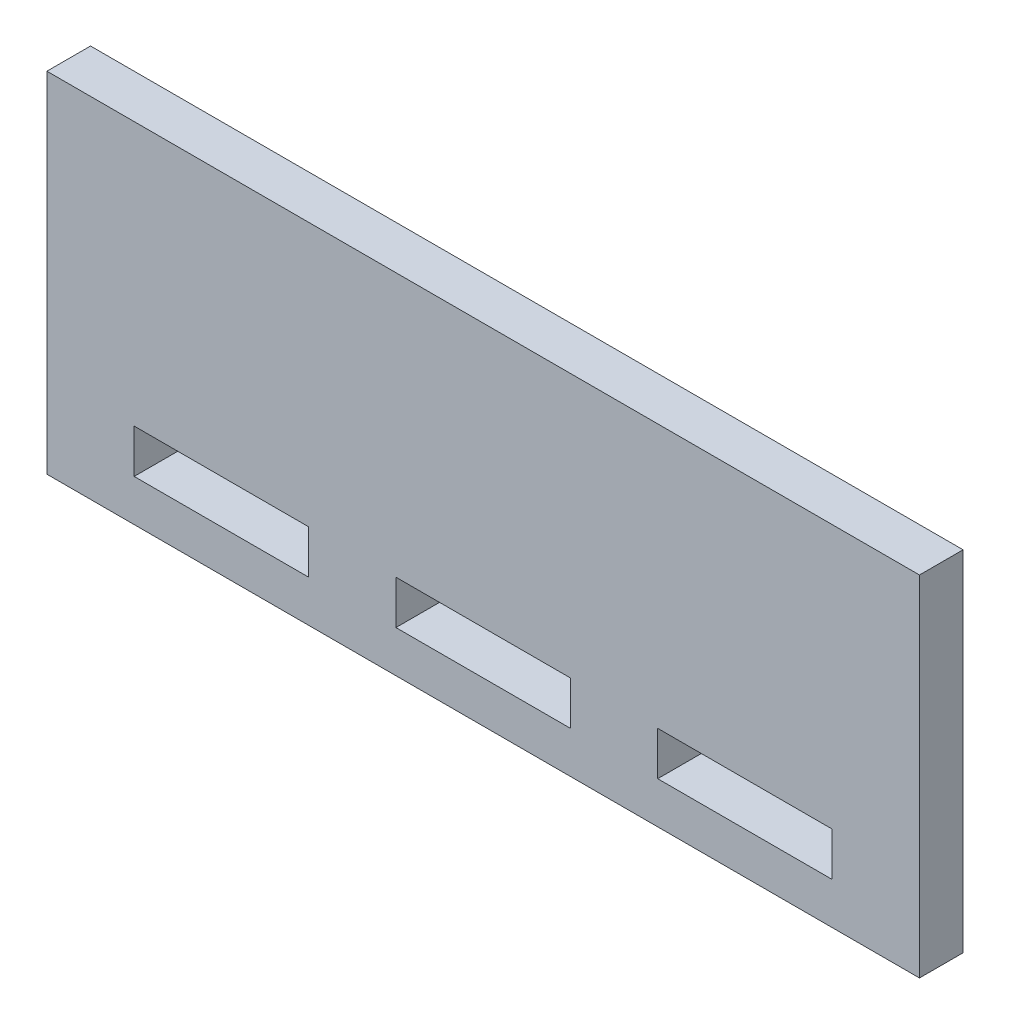
SolidWorks part; units mm, degrees
ref_plane "Front Plane" through (0, 0, 0) normal (0, 0, 1) x (1, 0, 0)
ref_plane "Top Plane" through (0, 0, 0) normal (0, 1, 0) x (1, 0, 0)
ref_plane "Right Plane" through (0, 0, 0) normal (1, 0, 0) x (0, 0, -1)
sketch "Sketch1" plane through (0, 0, 0) normal (0, 1, 0) x (1, 0, 0)
  line L0 (0, 15.4483) -> (0, 24.666) construction
  line L1 (-63.5, 3.175) -> (63.5, 3.175)
  line L2 (-63.5, 3.175) -> (-63.5, -3.175)
  line L3 (-63.5, -3.175) -> (63.5, -3.175)
  line L4 (63.5, 3.175) -> (63.5, -3.175)
  line L5 (8.1935, 0) -> (24.922, 0) construction
  dimension "D1" = 127
  dimension "D2" = 6.35
extrude "Boss-Extrude1" add sketch "Sketch1" along normal blind 50.8
sketch "Sketch4" plane through (0, 0, 3.175) normal (0, 0, 1) x (1, 0, 0)
  line L0 (63.5, 12.4198) -> (-63.5, 12.4198) construction
  line L1 (-50.8, 12.4198) -> (-25.4, 12.4198)
  line L2 (-50.8, 12.4198) -> (-50.8, 6.0698)
  line L3 (-50.8, 6.0698) -> (-25.4, 6.0698)
  line L4 (-25.4, 12.4198) -> (-25.4, 6.0698)
  line L5 (-12.7, 12.4198) -> (12.7, 12.4198)
  line L6 (-12.7, 12.4198) -> (-12.7, 6.0698)
  line L7 (-12.7, 6.0698) -> (12.7, 6.0698)
  line L8 (12.7, 12.4198) -> (12.7, 6.0698)
  line L9 (25.4, 12.4198) -> (50.8, 12.4198)
  line L10 (25.4, 12.4198) -> (25.4, 6.0698)
  line L11 (25.4, 6.0698) -> (50.8, 6.0698)
  line L12 (50.8, 12.4198) -> (50.8, 6.0698)
  line L13 (399.5104, 6.0698) -> (63.5, 6.0698) construction
  line L14 (63.5, 12.4198) -> (-63.5, 12.4198) construction
  line L15 (399.5104, 6.0698) -> (63.5, 6.0698) construction
  line L16 (-63.5, 50.8) -> (-63.5, 0) construction
  dimension "D1" = 25.4
  dimension "D2" = 25.4
  dimension "D3" = 25.4
  dimension "D4" = 12.7
  dimension "D5" = 12.7
  dimension "D6" = 12.7
extrude "Cut-Extrude2" cut sketch "Sketch4" against normal through all
